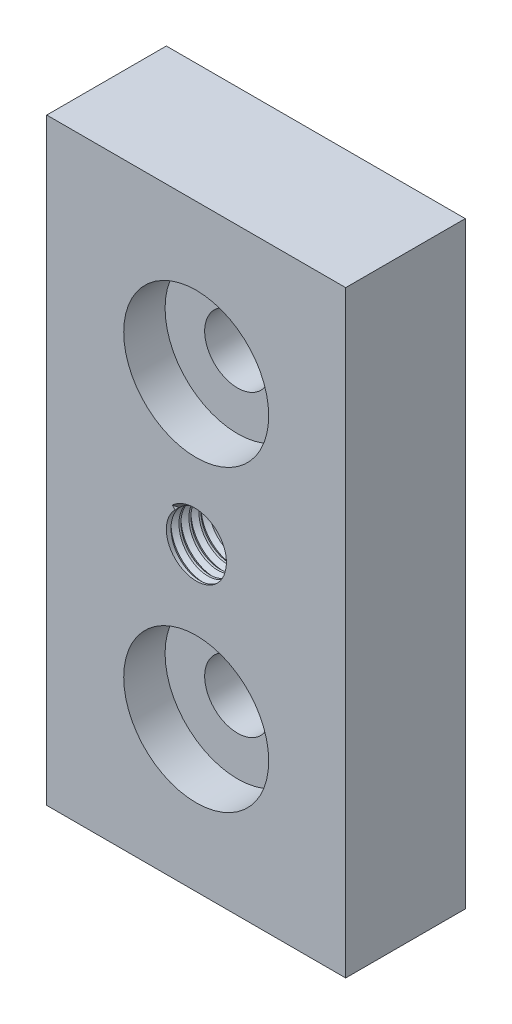
SolidWorks part; units mm, degrees
ref_plane "前视基准面" through (0, 0, 0) normal (0, 0, 1) x (1, 0, 0)
ref_plane "上视基准面" through (0, 0, 0) normal (0, 1, 0) x (1, 0, 0)
ref_plane "右视基准面" through (0, 0, 0) normal (1, 0, 0) x (0, 0, -1)
sketch "草图1" plane through (0, 0, 0) normal (0, 0, 1) x (1, 0, 0)
  line L1 (-15, 30) -> (15, 30)
  line L2 (-15, 30) -> (-15, -30)
  line L3 (-15, -30) -> (15, -30)
  line L4 (15, 30) -> (15, -30)
  line L5 (-15, 30) -> (15, -30) construction
  line L6 (-15, -30) -> (15, 30) construction
  point P0 (0, 0)
  dimension "D1" = 30
  dimension "D2" = 60
extrude "凸台-拉伸1" add sketch "草图1" along normal blind 12
hole_wizard "M6 六角头螺钉的柱形沉头孔1" positions "草图5" profile "草图4" counterbore size "M6" standard "Ansi Metric" end condition through all
sketch "草图5" plane through (0, 0, 12) normal (0, 0, 1) x (1, 0, 0)
  point P0 (0, 15)
  point P1 (0, -15)
  point P9 (0, 0)
  dimension "D1" = 15
  dimension "D2" = 15
sketch "草图4" plane through (0, 15, 12) normal (1, 0, 0) x (0, -1, 0)
  line L0 (0, 0) -> (0, 12)
  line L1 (0, 12) -> (3.3, 12)
  line L3 (3.3, 12) -> (3.3, 4.15)
  line L4 (3.3, 4.15) -> (7.275, 4.15)
  line L5 (7.275, 4.15) -> (7.275, 0)
  line L7 (7.275, 0) -> (0, 0)
  line L11 (0, -6.35) -> (0, 107.95) construction
  dimension "通孔孔直径" = 6.6
  dimension "通孔孔深度" = 12
  dimension "柱形沉头孔直径" = 14.55
  dimension "柱形沉头孔深度" = 4.15
sketch "草图6" plane through (0, 0, 12) normal (0, 0, 1) x (1, 0, 0)
  circle A0 centre (0, 0) radius 3
  dimension "D1" = 6
extrude "切除-拉伸1" cut sketch "草图6" against normal through all
sketch "草图7" plane through (0, 0, 12) normal (0, 0, 1) x (1, 0, 0)
  circle A0 centre (0, 0) radius 3 construction
  circle A1 centre (0, 0) radius 3
curve "螺旋线/涡状线1" pitch 1 height 12 radius 3 centre (0, 0, 12) axis (0, 0, -1) start towards (-0.7071, 0.7071, 0)
sketch "草图8" plane through (0, 0, 0) normal (0, 1, 0) x (1, 0, 0)
  line L0 (3, -11.225) -> (3, -12.025)
  line L1 (3, -11.625) -> (3.4, -11.625) construction
  line L2 (3, -11.225) -> (3.4, -11.625)
  line L3 (3.4, -11.625) -> (3, -12.025)
  dimension "D1" = 0.8
  dimension "D2" = 0.4
sweep "切除-扫描1" cut profiles "草图8" path "螺旋线/涡状线1"
